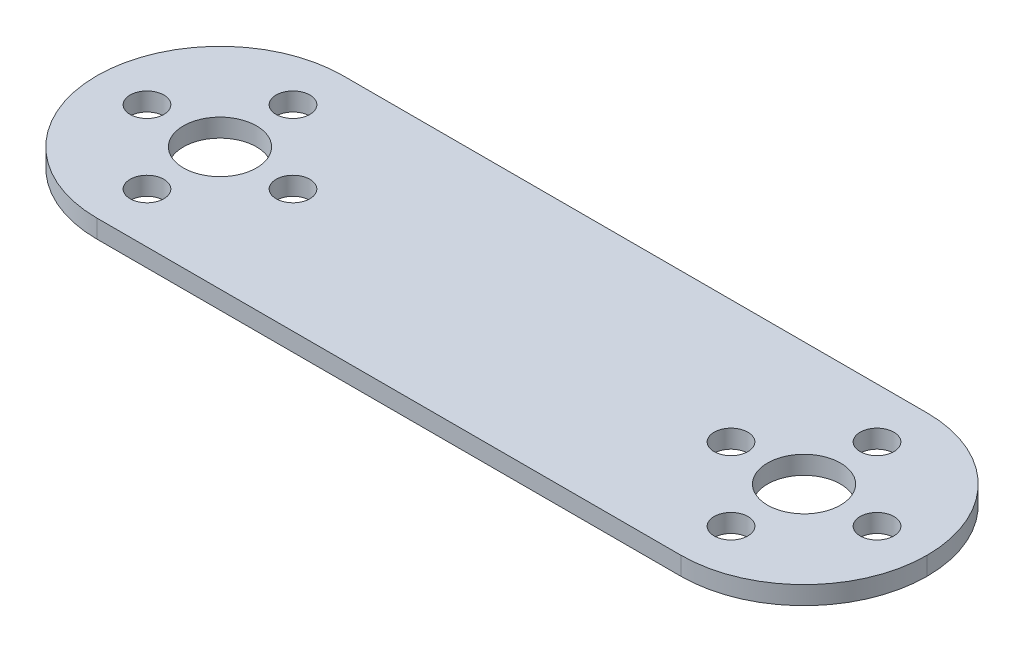
SolidWorks part; units mm, degrees
ref_plane "Front Plane" through (0, 0, 0) normal (0, 0, 1) x (1, 0, 0)
ref_plane "Top Plane" through (0, 0, 0) normal (0, 1, 0) x (1, 0, 0)
ref_plane "Right Plane" through (0, 0, 0) normal (1, 0, 0) x (0, 0, -1)
sketch "Sketch1" plane through (0, 0, 0) normal (0, 1, 0) x (1, 0, 0)
  line L1 (-45.5, 13.5) -> (45.5, 13.5)
  line L2 (-45.5, 13.5) -> (-45.5, -13.5)
  line L3 (-45.5, -13.5) -> (45.5, -13.5)
  line L4 (45.5, 13.5) -> (45.5, -13.5)
  line L5 (-45.5, 13.5) -> (45.5, -13.5) construction
  line L6 (-45.5, -13.5) -> (45.5, 13.5) construction
  point P0 (0, 0)
  dimension "D1" = 91
  dimension "D2" = 27
extrude "Boss-Extrude1" add sketch "Sketch1" along normal blind 2
sketch "Sketch2" plane through (0, 2, 0) normal (0, 1, 0) x (1, 0, 0)
  line L0 (-53.1996, 0) -> (63.0822, 0) construction
  circle B0 centre (-32, 0) radius 4
  circle B1 centre (-24, 0) radius 1.85
  circle B2 centre (-40, 0) radius 1.85
  circle B3 centre (-32, -8) radius 1.85
  circle B4 centre (-32, 8) radius 1.85
  circle B5 centre (32, 0) radius 4
  circle B6 centre (40, 0) radius 1.85
  circle B7 centre (24, 0) radius 1.85
  circle B8 centre (32, -8) radius 1.85
  circle B9 centre (32, 8) radius 1.85
  dimension "D1" = 32
  dimension "D2" = 32
sketch_block_instance "TETRIX 4 hole Pattern-1"
sketch_block "TETRIX 4 hole Pattern"
sketch_block_instance "TETRIX 4 hole Pattern-2"
extrude "Cut-Extrude1" cut sketch "Sketch2" against normal blind 2
fillet "Fillet1" radius 13.5 4 edges at (45.5, 1, 13.5) (45.5, 1, -13.5) (-45.5, 1, 13.5) (-45.5, 1, -13.5)
